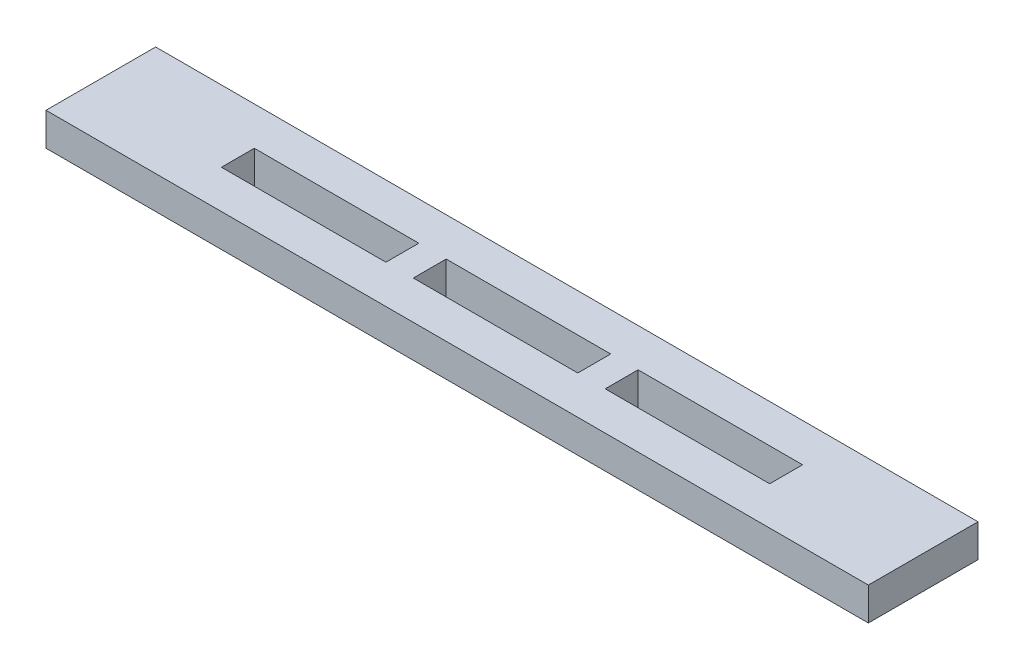
SolidWorks part; units mm, degrees
ref_plane "Front Plane" through (0, 0, 0) normal (0, 0, 1) x (1, 0, 0)
ref_plane "Top Plane" through (0, 0, 0) normal (0, 1, 0) x (1, 0, 0)
ref_plane "Right Plane" through (0, 0, 0) normal (1, 0, 0) x (0, 0, -1)
sketch "Sketch1" plane through (0, 0, 0) normal (0, 1, 0) x (1, 0, 0)
  line L1 (-75, 10) -> (75, 10)
  line L2 (-75, 10) -> (-75, -10)
  line L3 (-75, -10) -> (75, -10)
  line L4 (75, 10) -> (75, -10)
  line L5 (-75, 10) -> (75, -10) construction
  line L6 (-75, -10) -> (75, 10) construction
  point P0 (0, 0)
  dimension "D2" = 20
  dimension "D1" = 150
sketch "Sketch2" plane through (0, 0, 0) normal (0, 0, 1) x (1, 0, 0)
  line L0 (0, 0) -> (0, 6) construction
  line L1 (-75, 0) -> (75, 0) construction
extrude "Boss-Extrude1" add sketch "Sketch1" along normal up to vertex (6 mm away) contours L2 L3 L4 L1 up to point (0, 6, 0)
sketch "Sketch3" plane through (0, 6, 0) normal (0, 1, 0) x (1, 0, 0)
  line L0 (15, -3) -> (15, 3) construction
  line L1 (50, 3) -> (20, 3)
  line L2 (50, 3) -> (50, -3)
  line L3 (50, -3) -> (20, -3)
  line L4 (20, 3) -> (20, -3)
  line L5 (15, -3) -> (-15, -3)
  line L6 (15, -3) -> (15, 3)
  line L7 (15, 3) -> (-15, 3)
  line L8 (-15, -3) -> (-15, 3)
  line L10 (-50, 3) -> (-20, 3)
  line L11 (-50, 3) -> (-50, -3)
  line L12 (-50, -3) -> (-20, -3)
  line L13 (-20, 3) -> (-20, -3)
  point P19 (15, -1.6)
extrude "Cut-Extrude1" cut sketch "Sketch3" against normal through all
equation "\"glass_width\" = 150"
equation "\"glass_height\"= 100"
equation "\"glass_thickness\"= 4"
equation "\"brood_space\"= 42"
equation "\"t1\"= 6"
equation "\"t2\"= 3.2"
equation "\"box_depth\"= \"brood_space\" + \"glass_thickness\" + \"glass_thickness\" + \"t2\" + \"t2\""
equation "\"box_width\"= \"glass_width\" + \"t1\" + \"t1\""
equation "\"food_height\"= 70"
equation "\"box_height\" = \"glass_height\" + ( \"t1\" * 3 ) + \"food_height\""
equation "\"D1@Sketch2\"=\"t1\""
equation "\"D1@Sketch1\"=\"glass_width\""
